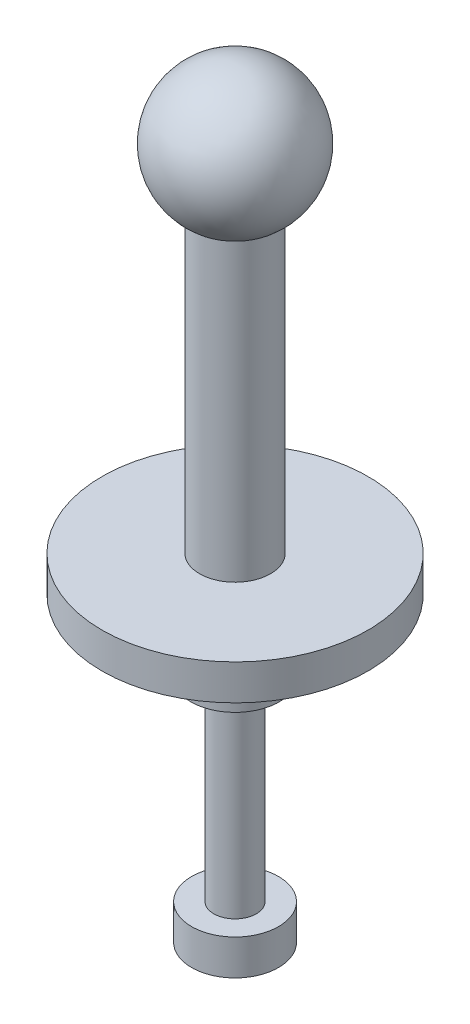
SolidWorks part; units mm, degrees
ref_plane "Front Plane" through (0, 0, 0) normal (0, 0, 1) x (1, 0, 0)
ref_plane "Top Plane" through (0, 0, 0) normal (0, 1, 0) x (1, 0, 0)
ref_plane "Right Plane" through (0, 0, 0) normal (1, 0, 0) x (0, 0, -1)
sketch "Sketch3" plane through (0, 0, 0) normal (0, 1, 0) x (1, 0, 0)
  circle A0 centre (0, 0) radius 7.5
  dimension "D1" = 15
extrude "Boss-Extrude1" add sketch "Sketch3" against normal blind 2 contours A0
sketch "Sketch4" plane through (0, 0, 0) normal (0, 0, 1) x (1, 0, 0)
  line L0 (0, -2) -> (0, -19)
  line L1 (-7.5, -2) -> (7.5, -2) construction
  line L2 (0, -19) -> (-2.45, -19)
  line L3 (-2.45, -19) -> (-2.45, -17)
  line L4 (-2.45, -17) -> (-1.2, -17)
  line L5 (-1.2, -17) -> (-1.2, -6)
  line L6 (-1.2, -6) -> (-2.5, -6)
  line L7 (-2.5, -6) -> (-2.5, -4.5)
  line L8 (-2.5, -4.5) -> (-1.2, -4.5)
  line L9 (-1.2, -4.5) -> (-1.2, -4)
  line L10 (-1.2, -4) -> (-4, -2)
  line L11 (0, -2) -> (-4, -2)
  dimension "D1" = 4
  dimension "D2" = 2
  dimension "D3" = 1.2
  dimension "D4" = 2.5
  dimension "D5" = 1.5
  dimension "D6" = 2
  dimension "D7" = 2.45
  dimension "D8" = 15
  dimension "D9" = 11
revolve "Revolve3" add sketch "Sketch4" angle 360 about L0 region at (-0.9542, -10.0146, 0)
sketch "Sketch5" plane through (0, 0, 0) normal (1, 0, 0) x (0, 0, -1)
  line L0 (0, 0) -> (0, 20) construction
  line L1 (0, 23.9) -> (0, 16.1)
  line L2 (-2, 0) -> (-2, 16.6519)
  line L3 (7.5, 0) -> (-7.5, 0) construction
  line L4 (2, 0) -> (2, 16.6519)
  line L5 (-2, 0) -> (2, 0)
  circle A0 centre (0, 20) radius 3.9
  dimension "D2" = 7.8
  dimension "D1" = 20
  dimension "D3" = 4
revolve "Revolve4" add sketch "Sketch5" angle 360 about L0 region at (0, 8.14, 1.0056) region at (0, 20, 1.6552)
